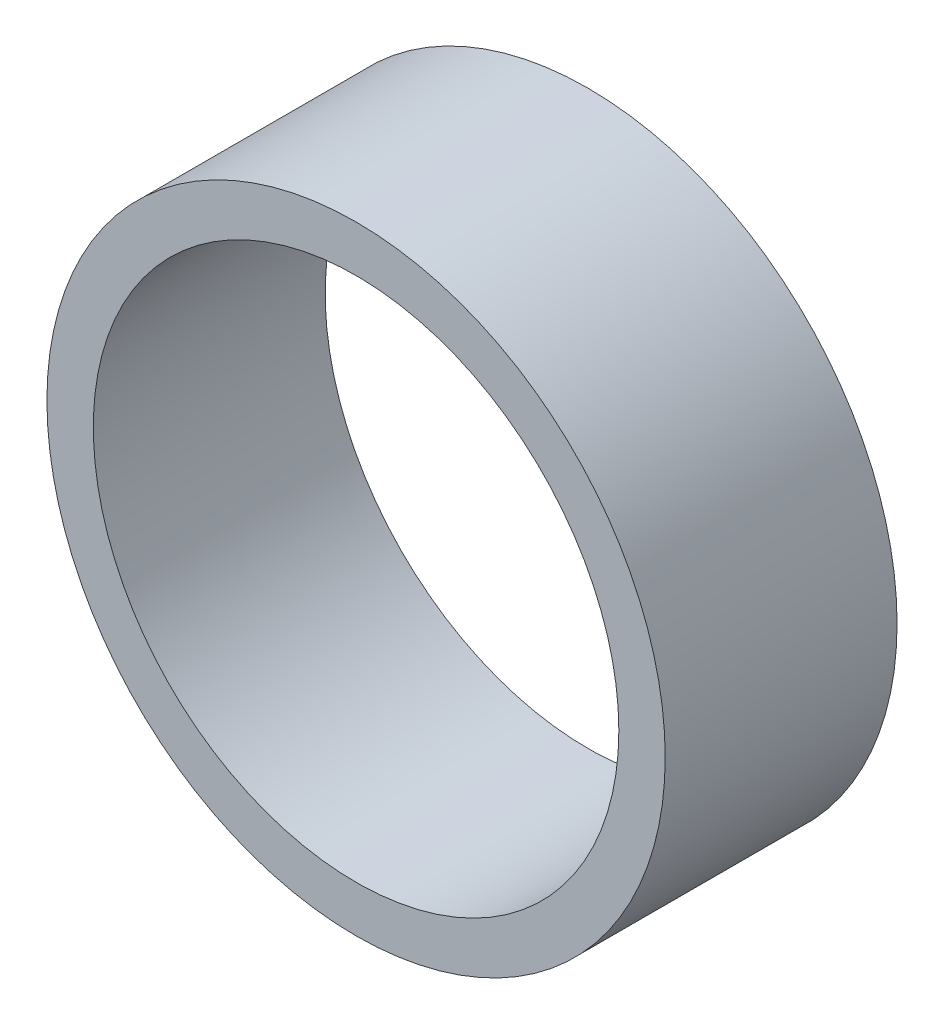
SolidWorks part; units mm, degrees
material "AISI Type 316L stainless steel"
ref_plane "Front Plane" through (0, 0, 0) normal (0, 0, 1) x (1, 0, 0)
ref_plane "Top Plane" through (0, 0, 0) normal (0, 1, 0) x (1, 0, 0)
ref_plane "Right Plane" through (0, 0, 0) normal (1, 0, 0) x (0, 0, -1)
sketch "Sketch1" plane through (0, 0, 0) normal (0, 0, 1) x (1, 0, 0)
  circle A0 centre (0, 0) radius 5.1
  circle A1 centre (0, 0) radius 6
  dimension "D1" = 10.2
  dimension "D2" = 12
extrude "Boss-Extrude1" add sketch "Sketch1" along normal blind 4.5
